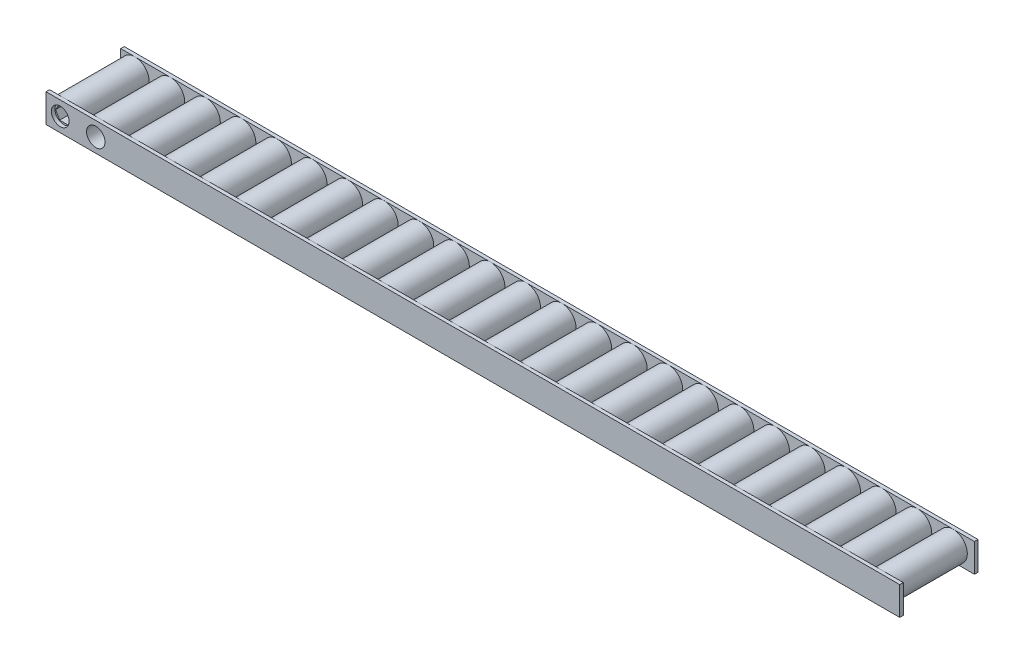
SolidWorks part; units mm, degrees
note: '?' marks a value the reader was unsure of.
material "6061 Alloy"
ref_plane "Front Plane" through (0, 0, 0) normal (0, 0, 1) x (1, 0, 0)
ref_plane "Top Plane" through (0, 0, 0) normal (0, 1, 0) x (1, 0, 0)
ref_plane "Right Plane" through (0, 0, 0) normal (1, 0, 0) x (0, 0, -1)
sketch "Sketch1" plane through (0, 0, 0) normal (0, 0, 1) x (1, 0, 0)
  circle A0 centre (0, 0) radius 12.7
  dimension "D1" = 25.4
extrude "Boss-Extrude1" add sketch "Sketch1" along normal blind 63.5 contours A0
pattern_linear "LPattern1" count 24 spacing 31.75 along (1, 0, 0) of "Boss-Extrude1"
sketch "Sketch2" plane through (0, 0, 63.5) normal (0, 0, 1) x (1, 0, 0)
  line L0 (-12.7, 12.7) -> (-12.7, -12.7)
  line L1 (-12.7, -12.7) -> (749.3, -12.7)
  line L2 (749.3, -12.7) -> (749.3, 12.7)
  line L3 (749.3, 12.7) -> (-12.7, 12.7)
  dimension "D1" = 762
  dimension "D2" = 25.4
extrude "Boss-Extrude2" add sketch "Sketch2" along normal blind 3.175
ref_plane "Plane1" through (0, 0, 31.75) normal (0, 0, 1) x (1, 0, 0)
mirror "Mirror1" about plane through (0, 0, 31.75) normal (0, 0, 1) of "Boss-Extrude2"
sketch "Sketch3" plane through (0, 0, 66.675) normal (0, 0, 1) x (1, 0, 0)
  line L1 (7.3323, 0) -> (3.6662, 6.35)
  line L2 (31.75, -12.7) -> (63.5, -12.7)
  line L3 (63.5, 12.7) -> (31.75, 12.7)
  line L6 (3.6662, 6.35) -> (-3.6662, 6.35)
  line L7 (-3.6662, 6.35) -> (-7.3323, 0)
  line L8 (-7.3323, 0) -> (-3.6662, -6.35)
  line L9 (-3.6662, -6.35) -> (3.6662, -6.35)
  line L10 (3.6662, -6.35) -> (7.3323, 0)
  arc A0 (0, 12.7) -> (-12.7, 0) centre (0, 0) ccw construction
  arc A1 (0, -12.7) -> (0, 12.7) centre (0, 0) ccw construction
  arc A2 (31.75, -12.7) -> (31.75, 12.7) centre (31.75, 0) ccw
  arc A3 (63.5, 12.7) -> (63.5, -12.7) centre (63.5, 0) ccw
  arc A4 (31.75, -12.7) -> (31.75, 12.7) centre (31.75, 0) ccw construction
  arc A6 (31.75, 12.7) -> (31.75, -12.7) centre (31.75, 0) ccw construction
  arc A7 (0, 12.7) -> (-12.7, 0) centre (0, 0) ccw construction
  arc A8 (0, -12.7) -> (0, 12.7) centre (0, 0) ccw construction
  arc A9 (31.75, 12.7) -> (31.75, -12.7) centre (31.75, 0) ccw construction
  circle A10 centre (31.75, 0) radius 8.255
  circle A11 centre (0, 0) radius 6.35 construction
  dimension "D2" = 16.51
  dimension "D3" = 12.7
  dimension "D1" = 0
extrude "Cut-Extrude1" cut sketch "Sketch3" against normal through all
ref_axis "Axis1" through (539.75, 0, 63.5) along (0, 0, -1)?
ref_axis "Axis2" through (571.5, 0, 63.5) along (0, 0, -1)?
ref_axis "Axis3" through (603.25, 0, 63.5) along (0, 0, -1)?
sketch "Sketch4" plane through (0, 0, 66.675) normal (0, 0, 1) x (1, 0, 0)
  circle A0 centre (730.25, 0) radius 9.525
  circle A1 centre (730.25, 0) radius 12.7
  circle A2 centre (730.25, 0) radius 12.7 construction
  dimension "D1" = 0
sketch "Sketch6" plane through (0, 0, 66.675) normal (0, 0, 1) x (1, 0, 0)
  circle A0 centre (0, 0) radius 7.9375
  dimension "D1" = 15.875
extrude "Cut-Extrude2" cut sketch "Sketch6" against normal blind 3.175
mirror "Mirror2" about plane through (0, 0, 31.75) normal (0, 0, 1) of "Cut-Extrude2"
